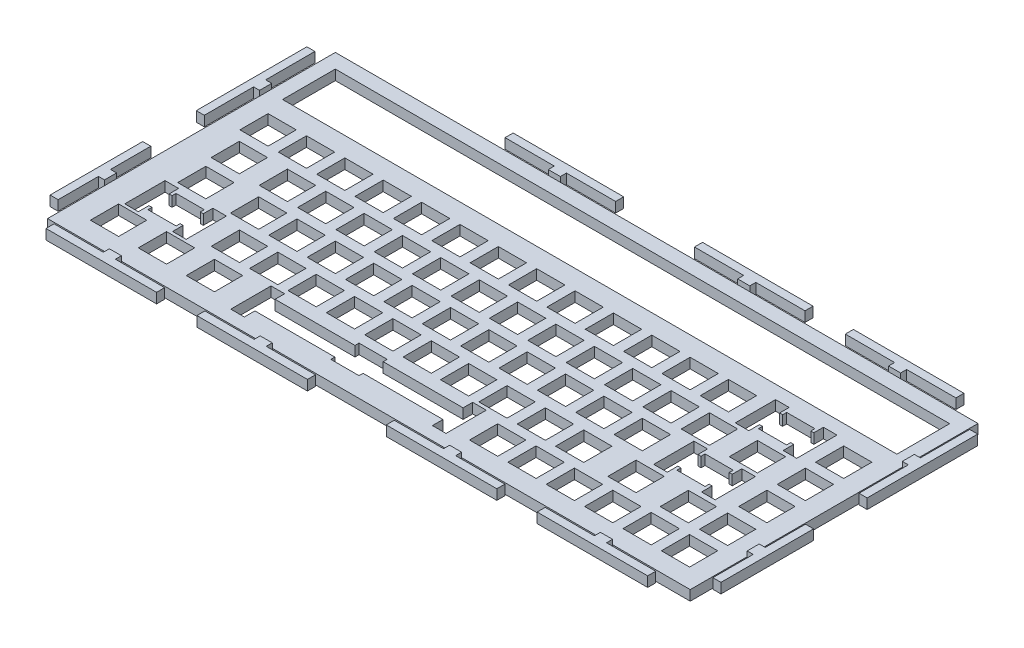
SolidWorks part; units mm, degrees
ref_plane "Front Plane" through (0, 0, 0) normal (0, 0, 1) x (1, 0, 0)
ref_plane "Top Plane" through (0, 0, 0) normal (0, 1, 0) x (1, 0, 0)
ref_plane "Right Plane" through (0, 0, 0) normal (1, 0, 0) x (0, 0, -1)
sketch "Sketch1" plane through (0, 0, 0) normal (0, 1, 0) x (1, 0, 0)
  line L2 (-75.7545, 37.9956) -> (-61.7545, 37.9956)
  line L3 (-94.8265, 37.9956) -> (-80.8265, 37.9956)
  line L4 (-94.8265, 37.9956) -> (-94.8265, 51.9956)
  line L5 (-94.8265, 51.9956) -> (-80.8265, 51.9956)
  line L6 (-80.8265, 37.9956) -> (-80.8265, 51.9956)
  line L7 (-75.7545, 37.9956) -> (-75.7545, 51.9956)
  line L8 (-75.7545, 51.9956) -> (-61.7545, 51.9956)
  line L9 (-61.7545, 37.9956) -> (-61.7545, 51.9956)
  line L10 (133.7495, 37.9956) -> (147.7495, 37.9956)
  line L11 (-37.6545, 37.9956) -> (-23.6545, 37.9956)
  line L12 (-56.7045, 37.9956) -> (-42.7045, 37.9956)
  line L13 (-56.7045, 37.9956) -> (-56.7045, 51.9956)
  line L14 (-56.7045, 51.9956) -> (-42.7045, 51.9956)
  line L15 (-42.7045, 37.9956) -> (-42.7045, 51.9956)
  line L16 (-37.6545, 37.9956) -> (-37.6545, 51.9956)
  line L17 (-37.6545, 51.9956) -> (-23.6545, 51.9956)
  line L18 (-23.6545, 37.9956) -> (-23.6545, 51.9956)
  line L19 (133.7495, 37.9956) -> (133.7495, 51.9956)
  line L20 (133.7495, 51.9956) -> (147.7495, 51.9956)
  line L21 (0.4455, 37.9956) -> (14.4455, 37.9956)
  line L22 (-18.6045, 37.9956) -> (-4.6045, 37.9956)
  line L23 (-18.6045, 37.9956) -> (-18.6045, 51.9956)
  line L24 (-18.6045, 51.9956) -> (-4.6045, 51.9956)
  line L25 (-4.6045, 37.9956) -> (-4.6045, 51.9956)
  line L26 (0.4455, 37.9956) -> (0.4455, 51.9956)
  line L27 (0.4455, 51.9956) -> (14.4455, 51.9956)
  line L28 (14.4455, 37.9956) -> (14.4455, 51.9956)
  line L29 (147.7495, 37.9956) -> (147.7495, 51.9956)
  line L30 (38.5455, 37.9956) -> (52.5455, 37.9956)
  line L31 (19.4955, 37.9956) -> (33.4955, 37.9956)
  line L32 (19.4955, 37.9956) -> (19.4955, 51.9956)
  line L33 (19.4955, 51.9956) -> (33.4955, 51.9956)
  line L34 (33.4955, 37.9956) -> (33.4955, 51.9956)
  line L35 (38.5455, 37.9956) -> (38.5455, 51.9956)
  line L36 (38.5455, 51.9956) -> (52.5455, 51.9956)
  line L37 (52.5455, 37.9956) -> (52.5455, 51.9956)
  line L38 (147.7495, 44.9956) -> (154.1495, 44.9956) construction
  line L39 (167.1835, 18.9456) -> (181.1835, 18.9456)
  line L40 (167.1835, 18.9456) -> (167.1835, 32.9456)
  line L41 (76.6455, 37.9956) -> (90.6455, 37.9956)
  line L42 (57.5955, 37.9956) -> (71.5955, 37.9956)
  line L43 (57.5955, 37.9956) -> (57.5955, 51.9956)
  line L44 (57.5955, 51.9956) -> (71.5955, 51.9956)
  line L45 (71.5955, 37.9956) -> (71.5955, 51.9956)
  line L46 (76.6455, 37.9956) -> (76.6455, 51.9956)
  line L47 (76.6455, 51.9956) -> (90.6455, 51.9956)
  line L48 (90.6455, 37.9956) -> (90.6455, 51.9956)
  line L49 (167.1835, 32.9456) -> (181.1835, 32.9456)
  line L50 (114.7225, 37.9956) -> (128.7225, 37.9956)
  line L51 (95.6955, 37.9956) -> (109.6955, 37.9956)
  line L52 (95.6955, 37.9956) -> (95.6955, 51.9956)
  line L53 (95.6955, 51.9956) -> (109.6955, 51.9956)
  line L54 (109.6955, 37.9956) -> (109.6955, 51.9956)
  line L55 (114.7225, 37.9956) -> (114.7225, 51.9956)
  line L56 (114.7225, 51.9956) -> (128.7225, 51.9956)
  line L57 (128.7225, 37.9956) -> (128.7225, 51.9956)
  line L58 (181.1835, 18.9456) -> (181.1835, 32.9456)
  line L59 (157.3735, 25.9456) -> (167.1835, 25.9456) construction
  line L73 (162.3995, 52.2456) -> (176.3995, 52.2456)
  line L75 (176.3995, 38.2456) -> (162.3995, 38.2456)
  line L77 (176.3995, 52.2456) -> (176.3995, 50.2456)
  line L78 (176.3995, 50.2456) -> (177.8995, 50.2456)
  line L79 (177.8995, 50.2456) -> (177.8995, 54.9956)
  line L80 (177.8995, 54.9956) -> (184.6495, 54.9956)
  line L81 (184.6495, 54.9956) -> (184.6495, 34.9956)
  line L82 (184.6495, 34.9956) -> (177.8995, 34.9956)
  line L83 (177.8995, 34.9956) -> (177.8995, 40.2456)
  line L84 (177.8995, 40.2456) -> (176.3995, 40.2456)
  line L85 (176.3995, 40.2456) -> (176.3995, 38.2456)
  line L86 (162.3995, 52.2456) -> (162.3995, 50.2456)
  line L87 (160.8995, 54.9956) -> (160.8995, 50.2456)
  line L88 (160.8995, 50.2456) -> (162.3995, 50.2456)
  line L89 (160.8995, 54.9956) -> (154.1495, 54.9956)
  line L90 (154.1495, 54.9956) -> (154.1495, 34.9956)
  line L91 (154.1495, 34.9956) -> (160.8995, 34.9956)
  line L92 (160.8995, 34.9956) -> (160.8995, 40.2456)
  line L93 (160.8995, 40.2456) -> (162.3995, 40.2456)
  line L94 (162.3995, 40.2456) -> (162.3995, 38.2456)
  line L116 (-47.1265, 18.9456) -> (-33.1265, 18.9456)
  line L117 (-66.1765, 18.9456) -> (-52.1765, 18.9456)
  line L118 (-66.1765, 18.9456) -> (-66.1765, 32.9456)
  line L119 (-66.1765, 32.9456) -> (-52.1765, 32.9456)
  line L120 (-52.1765, 18.9456) -> (-52.1765, 32.9456)
  line L121 (-47.1265, 18.9456) -> (-47.1265, 32.9456)
  line L122 (-47.1265, 32.9456) -> (-33.1265, 32.9456)
  line L123 (-33.1265, 18.9456) -> (-33.1265, 32.9456)
  line L125 (-9.0515, 18.9456) -> (4.9485, 18.9456)
  line L126 (-28.0765, 18.9456) -> (-14.0765, 18.9456)
  line L127 (-28.0765, 18.9456) -> (-28.0765, 32.9456)
  line L128 (-28.0765, 32.9456) -> (-14.0765, 32.9456)
  line L129 (-14.0765, 18.9456) -> (-14.0765, 32.9456)
  line L130 (-9.0515, 18.9456) -> (-9.0515, 32.9456)
  line L131 (-9.0515, 32.9456) -> (4.9485, 32.9456)
  line L132 (4.9485, 18.9456) -> (4.9485, 32.9456)
  line L135 (29.0735, 18.9456) -> (43.0735, 18.9456)
  line L136 (9.9485, 18.9456) -> (23.9485, 18.9456)
  line L137 (9.9485, 18.9456) -> (9.9485, 32.9456)
  line L138 (9.9485, 32.9456) -> (23.9485, 32.9456)
  line L139 (23.9485, 18.9456) -> (23.9485, 32.9456)
  line L140 (29.0735, 18.9456) -> (29.0735, 32.9456)
  line L141 (29.0735, 32.9456) -> (43.0735, 32.9456)
  line L142 (43.0735, 18.9456) -> (43.0735, 32.9456)
  line L144 (67.1485, 18.9456) -> (81.1485, 18.9456)
  line L145 (48.1235, 18.9456) -> (62.1235, 18.9456)
  line L146 (48.1235, 18.9456) -> (48.1235, 32.9456)
  line L147 (48.1235, 32.9456) -> (62.1235, 32.9456)
  line L148 (62.1235, 18.9456) -> (62.1235, 32.9456)
  line L149 (67.1485, 18.9456) -> (67.1485, 32.9456)
  line L150 (67.1485, 32.9456) -> (81.1485, 32.9456)
  line L151 (81.1485, 18.9456) -> (81.1485, 32.9456)
  line L152 (159.9865, 14.1456) -> (173.9865, 14.1456)
  line L153 (-42.3635, -0.1044) -> (-28.3635, -0.1044)
  line L154 (-61.4135, -0.1044) -> (-47.4135, -0.1044)
  line L155 (105.2735, 18.9456) -> (119.2735, 18.9456)
  line L156 (86.2235, 18.9456) -> (100.2235, 18.9456)
  line L157 (86.2235, 18.9456) -> (86.2235, 32.9456)
  line L158 (86.2235, 32.9456) -> (100.2235, 32.9456)
  line L159 (100.2235, 18.9456) -> (100.2235, 32.9456)
  line L160 (105.2735, 18.9456) -> (105.2735, 32.9456)
  line L161 (105.2735, 32.9456) -> (119.2735, 32.9456)
  line L162 (119.2735, 18.9456) -> (119.2735, 32.9456)
  line L163 (-61.4135, -0.1044) -> (-61.4135, 13.8956)
  line L172 (-94.8265, 37.9956) -> (-94.8265, 32.9456) construction
  line L173 (-61.4135, 13.8956) -> (-47.4135, 13.8956)
  line L174 (-47.4135, -0.1044) -> (-47.4135, 13.8956)
  line L175 (-90.0635, 18.9456) -> (-76.0635, 18.9456)
  line L176 (-90.0635, 18.9456) -> (-90.0635, 32.9456)
  line L177 (-90.0635, 32.9456) -> (-76.0635, 32.9456)
  line L178 (-76.0635, 18.9456) -> (-76.0635, 32.9456)
  line L179 (-94.8265, 32.9456) -> (-90.0635, 32.9456) construction
  line L180 (124.3235, 18.9456) -> (138.3235, 18.9456)
  line L185 (124.3235, 18.9456) -> (124.3235, 32.9456)
  line L186 (124.3235, 32.9456) -> (138.3235, 32.9456)
  line L187 (138.3235, 18.9456) -> (138.3235, 32.9456)
  line L188 (-42.3635, -0.1044) -> (-42.3635, 13.8956)
  line L189 (143.3735, 18.9456) -> (157.3735, 18.9456)
  line L190 (143.3735, 18.9456) -> (143.3735, 32.9456)
  line L191 (143.3735, 32.9456) -> (157.3735, 32.9456)
  line L192 (157.3735, 18.9456) -> (157.3735, 32.9456)
  line L193 (-42.3635, 13.8956) -> (-28.3635, 13.8956)
  line L194 (-28.3635, -0.1044) -> (-28.3635, 13.8956)
  line L195 (-4.2635, -0.1044) -> (9.7365, -0.1044)
  line L196 (-23.3135, -0.1044) -> (-9.3135, -0.1044)
  line L197 (-23.3135, -0.1044) -> (-23.3135, 13.8956)
  line L198 (-23.3135, 13.8956) -> (-9.3135, 13.8956)
  line L199 (-9.3135, -0.1044) -> (-9.3135, 13.8956)
  line L200 (-4.2635, -0.1044) -> (-4.2635, 13.8956)
  line L201 (-4.2635, 13.8956) -> (9.7365, 13.8956)
  line L202 (9.7365, -0.1044) -> (9.7365, 13.8956)
  line L203 (33.8365, -0.1044) -> (47.8365, -0.1044)
  line L204 (14.7865, -0.1044) -> (28.7865, -0.1044)
  line L205 (14.7865, -0.1044) -> (14.7865, 13.8956)
  line L206 (14.7865, 13.8956) -> (28.7865, 13.8956)
  line L207 (28.7865, -0.1044) -> (28.7865, 13.8956)
  line L208 (33.8365, -0.1044) -> (33.8365, 13.8956)
  line L209 (33.8365, 13.8956) -> (47.8365, 13.8956)
  line L210 (47.8365, -0.1044) -> (47.8365, 13.8956)
  line L211 (71.9365, -0.1044) -> (85.9365, -0.1044)
  line L212 (52.8865, -0.1044) -> (66.8865, -0.1044)
  line L213 (52.8865, -0.1044) -> (52.8865, 13.8956)
  line L214 (52.8865, 13.8956) -> (66.8865, 13.8956)
  line L215 (66.8865, -0.1044) -> (66.8865, 13.8956)
  line L216 (71.9365, -0.1044) -> (71.9365, 13.8956)
  line L217 (71.9365, 13.8956) -> (85.9365, 13.8956)
  line L218 (85.9365, -0.1044) -> (85.9365, 13.8956)
  line L219 (110.0365, -0.1044) -> (124.0365, -0.1044)
  line L220 (90.9865, -0.1044) -> (104.9865, -0.1044)
  line L221 (90.9865, -0.1044) -> (90.9865, 13.8956)
  line L222 (90.9865, 13.8956) -> (104.9865, 13.8956)
  line L223 (104.9865, -0.1044) -> (104.9865, 13.8956)
  line L224 (110.0365, -0.1044) -> (110.0365, 13.8956)
  line L225 (110.0365, 13.8956) -> (124.0365, 13.8956)
  line L226 (124.0365, -0.1044) -> (124.0365, 13.8956)
  line L227 (-87.6075, -0.1044) -> (-73.6075, -0.1044)
  line L228 (-87.6075, -0.1044) -> (-87.6075, 13.8956)
  line L229 (-87.6075, 13.8956) -> (-73.6075, 13.8956)
  line L230 (-73.6075, -0.1044) -> (-73.6075, 13.8956)
  line L231 (-90.0635, 18.9456) -> (-90.0635, 13.8956) construction
  line L232 (129.0865, -0.1044) -> (143.0865, -0.1044)
  line L233 (129.0865, -0.1044) -> (129.0865, 13.8956)
  line L234 (129.0865, 13.8956) -> (143.0865, 13.8956)
  line L235 (143.0865, -0.1044) -> (143.0865, 13.8956)
  line L240 (-90.0635, 13.8956) -> (-87.6075, 13.8956) construction
  line L241 (173.9865, 0.1456) -> (159.9865, 0.1456)
  line L242 (173.9865, 14.1456) -> (173.9865, 12.1456)
  line L243 (173.9865, 12.1456) -> (175.4865, 12.1456)
  line L244 (175.4865, 12.1456) -> (175.4865, 16.8956)
  line L245 (175.4865, 16.8956) -> (182.2365, 16.8956)
  line L246 (182.2365, 16.8956) -> (182.2365, -3.1044)
  line L247 (182.2365, -3.1044) -> (175.4865, -3.1044)
  line L248 (175.4865, -3.1044) -> (175.4865, 2.1456)
  line L249 (175.4865, 2.1456) -> (173.9865, 2.1456)
  line L250 (173.9865, 2.1456) -> (173.9865, 0.1456)
  line L251 (159.9865, 14.1456) -> (159.9865, 12.1456)
  line L252 (158.4865, 16.8956) -> (158.4865, 12.1456)
  line L253 (158.4865, 12.1456) -> (159.9865, 12.1456)
  line L254 (158.4865, 16.8956) -> (151.7365, 16.8956)
  line L255 (151.7365, 16.8956) -> (151.7365, -3.1044)
  line L256 (151.7365, -3.1044) -> (158.4865, -3.1044)
  line L257 (158.4865, -3.1044) -> (158.4865, 2.1456)
  line L258 (158.4865, 2.1456) -> (159.9865, 2.1456)
  line L259 (159.9865, 2.1456) -> (159.9865, 0.1456)
  line L260 (143.0865, 12.1456) -> (151.7365, 12.1456) construction
  line L262 (-32.8385, -19.1544) -> (-18.8385, -19.1544)
  line L263 (-51.8885, -19.1544) -> (-37.8885, -19.1544)
  line L264 (-51.8885, -19.1544) -> (-51.8885, -5.1544)
  line L265 (-51.8885, -5.1544) -> (-37.8885, -5.1544)
  line L266 (-37.8885, -19.1544) -> (-37.8885, -5.1544)
  line L267 (-32.8385, -19.1544) -> (-32.8385, -5.1544)
  line L268 (-32.8385, -5.1544) -> (-18.8385, -5.1544)
  line L269 (-18.8385, -19.1544) -> (-18.8385, -5.1544)
  line L270 (5.2615, -19.1544) -> (19.2615, -19.1544)
  line L271 (-13.7885, -19.1544) -> (0.2115, -19.1544)
  line L272 (-13.7885, -19.1544) -> (-13.7885, -5.1544)
  line L273 (-13.7885, -5.1544) -> (0.2115, -5.1544)
  line L274 (0.2115, -19.1544) -> (0.2115, -5.1544)
  line L275 (5.2615, -19.1544) -> (5.2615, -5.1544)
  line L276 (5.2615, -5.1544) -> (19.2615, -5.1544)
  line L277 (19.2615, -19.1544) -> (19.2615, -5.1544)
  line L278 (43.3615, -19.1544) -> (57.3615, -19.1544)
  line L279 (24.3115, -19.1544) -> (38.3115, -19.1544)
  line L280 (24.3115, -19.1544) -> (24.3115, -5.1544)
  line L281 (24.3115, -5.1544) -> (38.3115, -5.1544)
  line L282 (38.3115, -19.1544) -> (38.3115, -5.1544)
  line L283 (43.3615, -19.1544) -> (43.3615, -5.1544)
  line L284 (43.3615, -5.1544) -> (57.3615, -5.1544)
  line L285 (57.3615, -19.1544) -> (57.3615, -5.1544)
  line L286 (81.4615, -19.6544) -> (95.4615, -19.6544)
  line L287 (62.4115, -19.6544) -> (76.4115, -19.6544)
  line L288 (62.4115, -19.6544) -> (62.4115, -5.6544)
  line L289 (62.4115, -5.6544) -> (76.4115, -5.6544)
  line L290 (76.4115, -19.6544) -> (76.4115, -5.6544)
  line L291 (81.4615, -19.6544) -> (81.4615, -5.6544)
  line L292 (81.4615, -5.6544) -> (95.4615, -5.6544)
  line L293 (95.4615, -19.6544) -> (95.4615, -5.6544)
  line L294 (119.5615, -19.6544) -> (133.5615, -19.6544)
  line L295 (100.5115, -19.6544) -> (114.5115, -19.6544)
  line L296 (100.5115, -19.6544) -> (100.5115, -5.6544)
  line L297 (100.5115, -5.6544) -> (114.5115, -5.6544)
  line L298 (114.5115, -19.6544) -> (114.5115, -5.6544)
  line L299 (119.5615, -19.6544) -> (119.5615, -5.6544)
  line L300 (119.5615, -5.6544) -> (133.5615, -5.6544)
  line L301 (133.5615, -19.6544) -> (133.5615, -5.6544)
  line L306 (-83.3445, -5.1544) -> (-69.3445, -5.1544)
  line L307 (145.5235, -19.6544) -> (159.5235, -19.6544)
  line L308 (145.5235, -19.6544) -> (145.5235, -5.6544)
  line L309 (145.5235, -5.6544) -> (159.5235, -5.6544)
  line L310 (159.5235, -19.6544) -> (159.5235, -5.6544)
  line L311 (-69.3445, -19.1544) -> (-83.3445, -19.1544)
  line L331 (171.4855, -19.6544) -> (185.4855, -19.6544)
  line L332 (171.4855, -19.6544) -> (171.4855, -5.6544)
  line L333 (171.4855, -5.6544) -> (185.4855, -5.6544)
  line L334 (185.4855, -19.6544) -> (185.4855, -5.6544)
  line L335 (159.5235, -12.6544) -> (171.4855, -12.6544) construction
  line L336 (-61.4135, -0.1044) -> (-61.4135, -5.1544) construction
  line L337 (-61.4135, -5.1544) -> (-51.8885, -5.1544) construction
  line L338 (-104.4215, 94.9896) -> (-117.5239, 94.9896) construction
  line L339 (-97.2765, 61.6456) -> (207.7235, 61.6456)
  line L340 (190.9955, 18.9456) -> (204.9955, 18.9456)
  line L341 (190.9955, 18.9456) -> (190.9955, 32.9456)
  line L342 (190.9955, 32.9456) -> (204.9955, 32.9456)
  line L343 (204.9955, 18.9456) -> (204.9955, 32.9456)
  line L344 (181.1835, 25.9456) -> (190.9955, 25.9456) construction
  line L345 (190.9745, 37.9956) -> (204.9745, 37.9956)
  line L346 (190.9745, 37.9956) -> (190.9745, 51.9956)
  line L347 (190.9745, 51.9956) -> (204.9745, 51.9956)
  line L348 (204.9745, 37.9956) -> (204.9745, 51.9956)
  line L349 (184.6495, 44.9956) -> (190.9745, 44.9956) construction
  line L350 (190.9425, -0.1044) -> (204.9425, -0.1044)
  line L351 (190.9425, -0.1044) -> (190.9425, 13.8956)
  line L352 (190.9425, 13.8956) -> (204.9425, 13.8956)
  line L353 (204.9425, -0.1044) -> (204.9425, 13.8956)
  line L354 (182.2365, 6.8956) -> (190.9425, 6.8956) construction
  line L355 (190.9855, -19.6544) -> (204.9855, -19.6544)
  line L356 (190.9855, -19.6544) -> (190.9855, -5.6544)
  line L357 (190.9855, -5.6544) -> (204.9855, -5.6544)
  line L358 (204.9855, -19.6544) -> (204.9855, -5.6544)
  line L359 (185.4855, -12.6544) -> (190.9855, -12.6544) construction
  line L360 (-69.3445, -5.1544) -> (-69.3445, -7.1544)
  line L361 (-69.3445, -7.1544) -> (-67.8445, -7.1544)
  line L362 (-67.8445, -7.1544) -> (-67.8445, -2.4044)
  line L363 (-67.8445, -2.4044) -> (-61.0945, -2.4044)
  line L364 (-61.0945, -2.4044) -> (-61.0945, -22.4044)
  line L365 (-61.0945, -22.4044) -> (-67.8445, -22.4044)
  line L366 (-67.8445, -22.4044) -> (-67.8445, -17.1544)
  line L367 (-67.8445, -17.1544) -> (-69.3445, -17.1544)
  line L368 (-69.3445, -17.1544) -> (-69.3445, -19.1544)
  line L369 (-83.3445, -5.1544) -> (-83.3445, -7.1544)
  line L370 (-84.8445, -2.4044) -> (-84.8445, -7.1544)
  line L371 (-84.8445, -7.1544) -> (-83.3445, -7.1544)
  line L372 (-84.8445, -2.4044) -> (-91.5945, -2.4044)
  line L373 (-91.5945, -2.4044) -> (-91.5945, -22.4044)
  line L374 (-91.5945, -22.4044) -> (-84.8445, -22.4044)
  line L375 (-84.8445, -22.4044) -> (-84.8445, -17.1544)
  line L376 (-84.8445, -17.1544) -> (-83.3445, -17.1544)
  line L377 (-83.3445, -17.1544) -> (-83.3445, -19.1544)
  line L378 (-93.0945, -37.9544) -> (-79.0945, -37.9544)
  line L379 (-93.0945, -37.9544) -> (-93.0945, -23.9544)
  line L380 (-93.0945, -23.9544) -> (-79.0945, -23.9544)
  line L381 (-79.0945, -37.9544) -> (-79.0945, -23.9544)
  line L382 (-69.2945, -37.9544) -> (-55.2945, -37.9544)
  line L383 (-69.2945, -37.9544) -> (-69.2945, -23.9544)
  line L384 (-69.2945, -23.9544) -> (-55.2945, -23.9544)
  line L385 (-55.2945, -37.9544) -> (-55.2945, -23.9544)
  line L390 (-45.4945, -37.9544) -> (-31.4945, -37.9544)
  line L391 (-45.4945, -37.9544) -> (-45.4945, -23.9544)
  line L392 (-45.4945, -23.9544) -> (-31.4945, -23.9544)
  line L393 (-31.4945, -37.9544) -> (-31.4945, -23.9544)
  line L394 (-55.2945, -23.9544) -> (-45.4945, -23.9544) construction
  line L395 (26.4395, -24.1144) -> (40.4395, -24.1144)
  line L396 (40.4395, -38.1144) -> (26.4395, -38.1144)
  line L397 (40.4395, -24.1144) -> (40.4395, -26.1144)
  line L398 (40.4395, -26.1144) -> (80.1235, -26.1144)
  line L399 (80.1235, -26.1144) -> (80.1235, -21.3644)
  line L400 (80.1235, -21.3644) -> (86.8735, -21.3644)
  line L401 (86.8735, -21.3644) -> (86.8735, -41.3644)
  line L402 (86.8735, -41.3644) -> (80.1235, -41.3644)
  line L403 (80.1235, -41.3644) -> (80.1235, -36.1144)
  line L404 (80.1235, -36.1144) -> (40.4395, -36.1144)
  line L405 (40.4395, -36.1144) -> (40.4395, -38.1144)
  line L406 (26.4395, -24.1144) -> (26.4395, -26.1144)
  line L407 (-13.2445, -21.3644) -> (-13.2445, -26.1144)
  line L408 (-13.2445, -26.1144) -> (26.4395, -26.1144)
  line L409 (-13.2445, -21.3644) -> (-19.9945, -21.3644)
  line L410 (-19.9945, -21.3644) -> (-19.9945, -41.3644)
  line L411 (-19.9945, -41.3644) -> (-13.2445, -41.3644)
  line L412 (-13.2445, -41.3644) -> (-13.2445, -36.1144)
  line L413 (-13.2445, -36.1144) -> (26.4395, -36.1144)
  line L414 (26.4395, -36.1144) -> (26.4395, -38.1144)
  line L415 (95.5435, -38.3644) -> (109.5435, -38.3644)
  line L416 (95.5435, -38.3644) -> (95.5435, -24.3644)
  line L417 (95.5435, -24.3644) -> (109.5435, -24.3644)
  line L418 (109.5435, -38.3644) -> (109.5435, -24.3644)
  line L419 (86.8735, -31.3644) -> (95.5435, -31.3644) construction
  line L420 (114.5935, -38.3644) -> (128.5935, -38.3644)
  line L421 (114.5935, -38.3644) -> (114.5935, -24.3644)
  line L422 (114.5935, -24.3644) -> (128.5935, -24.3644)
  line L423 (128.5935, -38.3644) -> (128.5935, -24.3644)
  line L424 (114.5935, -31.3644) -> (109.5435, -31.3644) construction
  line L425 (133.6435, -38.3644) -> (147.6435, -38.3644)
  line L426 (133.6435, -38.3644) -> (133.6435, -24.3644)
  line L427 (133.6435, -24.3644) -> (147.6435, -24.3644)
  line L428 (147.6435, -38.3644) -> (147.6435, -24.3644)
  line L429 (152.6935, -38.3644) -> (166.6935, -38.3644)
  line L430 (152.6935, -38.3644) -> (152.6935, -24.3644)
  line L431 (152.6935, -24.3644) -> (166.6935, -24.3644)
  line L432 (166.6935, -38.3644) -> (166.6935, -24.3644)
  line L433 (171.7435, -38.3644) -> (185.7435, -38.3644)
  line L434 (171.7435, -38.3644) -> (171.7435, -24.3644)
  line L435 (171.7435, -24.3644) -> (185.7435, -24.3644)
  line L436 (185.7435, -38.3644) -> (185.7435, -24.3644)
  line L437 (190.7935, -38.3644) -> (204.7935, -38.3644)
  line L438 (190.7935, -38.3644) -> (190.7935, -24.3644)
  line L439 (190.7935, -24.3644) -> (204.7935, -24.3644)
  line L440 (204.7935, -38.3644) -> (204.7935, -24.3644)
  line L441 (-97.2765, 61.6456) -> (-97.2765, 87.8456)
  line L442 (-97.2765, 87.8456) -> (207.7235, 87.8456)
  line L443 (207.7235, 61.6456) -> (207.7235, 87.8456)
  line L444 (-104.4215, 94.9896) -> (214.6585, 94.9896)
  line L445 (-104.4215, 94.9896) -> (-104.4215, -47.8854)
  line L446 (-104.4215, -47.8854) -> (214.6585, -47.8854)
  line L447 (214.6585, 94.9896) -> (214.6585, -47.8854)
  line L448 (-117.5239, 94.9896) -> (-117.5239, 25.8096) construction
  line L449 (-104.4215, -47.8854) -> (-117.5239, -47.8854) construction
  line L450 (-117.5239, -47.8854) -> (-117.5239, 14.6046) construction
  line L451 (-150.5498, 25.8096) -> (-98.6233, 25.8096) construction
  line L452 (-150.5498, 14.6046) -> (-97.2765, 14.6046) construction
  line L453 (-104.4215, 94.9896) -> (-104.4215, 60.3996) construction
  point P115 (128.7225, 44.9956)
  point P116 (154.1495, 44.9956)
  dimension "D1" = 14
  dimension "D2" = 20
  dimension "D3" = 4.75
  dimension "D4" = 6.75
  dimension "D5" = 1.5
  dimension "D6" = 2
  dimension "D13" = 14
  dimension "D14" = 14
  dimension "D15" = 5.072
  dimension "D16" = 14
  dimension "D17" = 5.05
  dimension "D18" = 5.05
  dimension "D19" = 14
  dimension "D20" = 4.763
  dimension "D21" = 5.05
  dimension "D22" = 9.887
  dimension "D23" = 26.2
  dimension "D24" = 14
  dimension "D25" = 14
  dimension "D26" = 5.05
  dimension "D27" = 5.05
  dimension "D28" = 5.05
  dimension "D29" = 5.05
  dimension "D30" = 5.05
  dimension "D31" = 5.05
  dimension "D32" = 5.05
  dimension "D33" = 5.05
  dimension "D34" = 5.05
  dimension "D35" = 5.027
  dimension "D36" = 5.05
  dimension "D37" = 5.05
  dimension "D38" = 5.025
  dimension "D39" = 5
  dimension "D40" = 5.125
  dimension "D41" = 5.05
  dimension "D42" = 5.025
  dimension "D43" = 5.075
  dimension "D44" = 5.05
  dimension "D45" = 5.05
  dimension "D46" = 5.027
  dimension "D47" = 14.65
  dimension "D48" = 14
  dimension "D49" = 9.81
  dimension "D50" = 12.194
  dimension "D51" = 5.05
  dimension "D52" = 5.05
  dimension "D53" = 5.05
  dimension "D54" = 5.05
  dimension "D55" = 5.05
  dimension "D56" = 5.05
  dimension "D57" = 5.05
  dimension "D58" = 5.05
  dimension "D59" = 5.05
  dimension "D60" = 5.05
  dimension "D61" = 14
  dimension "D62" = 20
  dimension "D63" = 5.05
  dimension "D64" = 2.456
  dimension "D65" = 4.75
  dimension "D66" = 6.75
  dimension "D67" = 1.5
  dimension "D68" = 2
  dimension "D69" = 16.9
  dimension "D70" = 14
  dimension "D71" = 5.05
  dimension "D72" = 5.05
  dimension "D73" = 5.05
  dimension "D74" = 5.05
  dimension "D75" = 5.05
  dimension "D76" = 5.05
  dimension "D77" = 5.05
  dimension "D78" = 5.05
  dimension "D79" = 5.05
  dimension "D80" = 11.962
  dimension "D81" = 20
  dimension "D82" = 14
  dimension "D83" = 11.962
  dimension "D84" = 14
  dimension "D85" = 14
  dimension "D86" = 9.812
  dimension "D87" = 14
  dimension "D88" = 14.575
  dimension "D89" = 4.75
  dimension "D90" = 14
  dimension "D91" = 6.75
  dimension "D92" = 14
  dimension "D93" = 16.956
  dimension "D94" = 14
  dimension "D95" = 5.5
  dimension "D96" = 5.05
  dimension "D97" = 5.05
  dimension "D98" = 9.525
  dimension "D99" = 1.5
  dimension "D100" = 2
  dimension "D101" = 5.05
  dimension "D102" = 9.206
  dimension "D103" = 5.05
  dimension "D104" = 14
  dimension "D105" = 14
  dimension "D106" = 14
  dimension "D107" = 14
  dimension "D108" = 1.5
  dimension "D109" = 9.8
  dimension "D110" = 5.05
  dimension "D111" = 9.8
  dimension "D112" = 5.05
  dimension "D113" = 5.05
  dimension "D114" = 14
  dimension "D115" = 14
  dimension "D116" = 20
  dimension "D117" = 4.75
  dimension "D118" = 6.75
  dimension "D119" = 39.684
  dimension "D120" = 2
  dimension "D121" = 5.05
  dimension "D122" = 11.5
  dimension "D123" = 14
  dimension "D124" = 8.67
  dimension "D125" = 5.25
  dimension "D126" = 14
  dimension "D127" = 5.05
  dimension "D128" = 14
  dimension "D129" = 14
  dimension "D130" = 14
  dimension "D131" = 14
  dimension "D132" = 5.05
  dimension "D133" = 5.05
  dimension "D134" = 5.05
  dimension "D135" = 5.05
  dimension "D136" = 4.8
  dimension "D137" = 5.25
  dimension "D138" = 5.25
  dimension "D139" = 5.25
  dimension "D140" = 305
  dimension "D141" = 9.65
  dimension "D142" = 142.875
  dimension "D143" = 319.08
  dimension "D144" = 7.144
  dimension "D145" = 7.145
  dimension "D146" = 2.45
  dimension "D147" = 69.18
  dimension "D148" = 62.49
extrude "Boss-Extrude2" add sketch "Sketch1" along normal mid plane 5
sketch "Sketch2" plane through (0, 2.5, 0) normal (0, 1, 0) x (1, 0, 0)
  line L0 (-104.4215, 25.7896) -> (-104.4215, 14.6146) construction
  line L1 (-104.4215, -47.8854) -> (-104.4215, 14.6146) construction
  line L2 (-104.4215, 94.9896) -> (-104.4215, -47.8854) construction
  line L3 (-104.4215, 94.9896) -> (-104.4215, 25.7896) construction
  line L4 (-104.4215, 60.3896) -> (-192.4203, 60.3896) construction
  line L5 (-104.4215, 63.3896) -> (-104.4215, 57.3896)
  line L6 (-104.4215, 63.3896) -> (-107.4215, 63.3896)
  line L7 (-104.4215, 57.3896) -> (-107.4215, 57.3896)
  line L8 (-107.4215, 63.3896) -> (-107.4215, 87.8456)
  line L9 (-107.4215, 57.3896) -> (-107.4215, 32.9456)
  line L10 (-107.4215, 87.8456) -> (-111.4215, 87.8456)
  line L11 (-111.4215, 87.8456) -> (-111.4215, 32.9456)
  line L12 (-111.4215, 32.9456) -> (-107.4215, 32.9456)
  line L13 (207.7235, 87.8456) -> (-97.2765, 87.8456) construction
  line L14 (-107.4215, 20.2021) -> (-104.4215, 20.2021) construction
  line L15 (-76.0635, 32.9456) -> (-90.0635, 32.9456) construction
  line L16 (-107.4215, 31.2421) -> (-107.4215, 9.1621) construction
  line L17 (-104.4215, -13.6354) -> (-104.4215, -19.6354)
  line L18 (-104.4215, -13.6354) -> (-107.4215, -13.6354)
  line L19 (-104.4215, -19.6354) -> (-107.4215, -19.6354)
  line L20 (-107.4215, -13.6354) -> (-107.4215, 6.3646)
  line L21 (-107.4215, 6.3646) -> (-111.4215, 6.3646)
  line L22 (-111.4215, 6.3646) -> (-111.4215, -39.6354)
  line L23 (-111.4215, -39.6354) -> (-107.4215, -39.6354)
  line L24 (-107.4215, -39.6354) -> (-107.4215, -19.6354)
  line L25 (214.6585, 14.5646) -> (214.6585, -47.8854) construction
  line L26 (55.1185, 125.0144) -> (55.1185, -78.0627) construction
  line L27 (221.6585, -39.6354) -> (217.6585, -39.6354)
  line L28 (221.6585, 6.3646) -> (221.6585, -39.6354)
  line L29 (217.6585, 6.3646) -> (221.6585, 6.3646)
  line L30 (217.6585, -13.6354) -> (217.6585, 6.3646)
  line L31 (214.6585, -13.6354) -> (217.6585, -13.6354)
  line L32 (214.6585, -13.6354) -> (214.6585, -19.6354)
  line L33 (214.6585, -19.6354) -> (217.6585, -19.6354)
  line L34 (217.6585, -39.6354) -> (217.6585, -19.6354)
  line L35 (214.6585, 63.3896) -> (217.6585, 63.3896)
  line L36 (217.6585, 63.3896) -> (217.6585, 87.8456)
  line L37 (217.6585, 87.8456) -> (221.6585, 87.8456)
  line L38 (221.6585, 87.8456) -> (221.6585, 32.9456)
  line L39 (221.6585, 32.9456) -> (217.6585, 32.9456)
  line L40 (217.6585, 57.3896) -> (217.6585, 32.9456)
  line L41 (214.6585, 57.3896) -> (217.6585, 57.3896)
  line L42 (214.6585, 63.3896) -> (214.6585, 57.3896)
  line L43 (214.6585, -47.8854) -> (214.6585, 94.9896) construction
  line L44 (214.6585, 94.9896) -> (214.6585, 25.7896) construction
  line L45 (214.6585, 25.7896) -> (214.6585, 14.5646) construction
  line L46 (214.6585, 20.1771) -> (217.6585, 20.1771) construction
  line L47 (217.6585, 31.2421) -> (217.6585, 9.1621) construction
  line L48 (55.1185, 94.9896) -> (55.1185, -47.8854) construction
  line L49 (214.6585, 94.9896) -> (-104.4215, 94.9896) construction
  line L50 (-104.4215, -47.8854) -> (214.6585, -47.8854) construction
  line L51 (55.1185, 23.4758) -> (270.1989, 23.4758) construction
  line L52 (55.1185, 23.4758) -> (-168.679, 23.4758) construction
  line L53 (214.6585, 94.9896) -> (56.9085, 94.9896) construction
  line L54 (-104.4215, 94.9896) -> (45.7235, 94.9896) construction
  line L55 (45.7235, 94.9896) -> (56.9085, 94.9896) construction
  line L56 (51.316, 94.9896) -> (51.316, 98.9896) construction
  line L57 (40.276, 98.9896) -> (62.356, 98.9896) construction
  line L58 (170.2335, 94.9896) -> (176.2335, 94.9896)
  line L59 (176.2335, 94.9896) -> (176.2335, 97.9896)
  line L60 (176.2335, 97.9896) -> (200.6835, 97.9896)
  line L61 (200.6835, 97.9896) -> (200.6835, 101.9896)
  line L62 (200.6835, 101.9896) -> (145.7835, 101.9896)
  line L63 (145.7835, 101.9896) -> (145.7835, 97.9896)
  line L64 (145.7835, 97.9896) -> (170.2335, 97.9896)
  line L65 (170.2335, 97.9896) -> (170.2335, 94.9896)
  line L66 (95.3335, 94.9896) -> (101.3335, 94.9896)
  line L67 (101.3335, 94.9896) -> (101.3335, 97.9896)
  line L68 (101.3335, 97.9896) -> (125.7835, 97.9896)
  line L69 (125.7835, 97.9896) -> (125.7835, 101.9896)
  line L70 (125.7835, 101.9896) -> (70.8835, 101.9896)
  line L71 (70.8835, 101.9896) -> (70.8835, 97.9896)
  line L72 (70.8835, 97.9896) -> (95.3335, 97.9896)
  line L73 (95.3335, 97.9896) -> (95.3335, 94.9896)
  line L74 (125.7835, 99.9896) -> (145.7835, 99.9896) construction
  line L75 (135.7835, 94.9896) -> (135.7835, 104.9896) construction
  line L84 (7.2985, 97.9896) -> (7.2985, 94.9896)
  line L85 (31.7485, 97.9896) -> (7.2985, 97.9896)
  line L86 (31.7485, 101.9896) -> (31.7485, 97.9896)
  line L87 (-23.1515, 101.9896) -> (31.7485, 101.9896)
  line L88 (-23.1515, 97.9896) -> (-23.1515, 101.9896)
  line L89 (1.2985, 97.9896) -> (-23.1515, 97.9896)
  line L90 (1.2985, 94.9896) -> (1.2985, 97.9896)
  line L91 (7.2985, 94.9896) -> (1.2985, 94.9896)
  line L92 (145.7835, -51.038) -> (170.2335, -51.038)
  line L93 (145.7835, -55.038) -> (145.7835, -51.038)
  line L94 (200.6835, -55.038) -> (145.7835, -55.038)
  line L95 (200.6835, -51.038) -> (200.6835, -55.038)
  line L96 (176.2335, -51.038) -> (200.6835, -51.038)
  line L97 (176.2335, -48.038) -> (176.2335, -51.038)
  line L98 (170.2335, -48.038) -> (176.2335, -48.038)
  line L99 (170.2335, -51.038) -> (170.2335, -48.038)
  line L100 (95.3335, -51.038) -> (95.3335, -48.038)
  line L101 (70.8835, -51.038) -> (95.3335, -51.038)
  line L102 (70.8835, -55.038) -> (70.8835, -51.038)
  line L103 (125.7835, -55.038) -> (70.8835, -55.038)
  line L104 (125.7835, -51.038) -> (125.7835, -55.038)
  line L105 (101.3335, -51.038) -> (125.7835, -51.038)
  line L106 (101.3335, -48.038) -> (101.3335, -51.038)
  line L107 (95.3335, -48.038) -> (101.3335, -48.038)
  line L108 (31.7485, -51.038) -> (7.2985, -51.038)
  line L109 (31.7485, -55.038) -> (31.7485, -51.038)
  line L110 (-23.1515, -55.038) -> (31.7485, -55.038)
  line L111 (-23.1515, -51.038) -> (-23.1515, -55.038)
  line L112 (1.2985, -51.038) -> (-23.1515, -51.038)
  line L113 (1.2985, -48.038) -> (1.2985, -51.038)
  line L114 (7.2985, -48.038) -> (1.2985, -48.038)
  line L115 (7.2985, -51.038) -> (7.2985, -48.038)
  line L116 (-43.1515, -55.038) -> (-43.1515, -51.038)
  line L117 (-98.0515, -55.038) -> (-43.1515, -55.038)
  line L118 (-98.0515, -51.038) -> (-98.0515, -55.038)
  line L119 (-73.6015, -51.038) -> (-98.0515, -51.038)
  line L120 (-73.6015, -48.038) -> (-73.6015, -51.038)
  line L121 (-67.6015, -48.038) -> (-73.6015, -48.038)
  line L122 (-67.6015, -51.038) -> (-67.6015, -48.038)
  line L123 (-43.1515, -51.038) -> (-67.6015, -51.038)
  line L124 (214.6585, -47.8854) -> (56.9135, -47.8854) construction
  line L125 (-104.4215, 94.9896) -> (-104.4215, 96.9896) construction
  line L126 (-104.4215, -47.8854) -> (45.7225, -47.8854) construction
  line L127 (45.7225, -47.8854) -> (56.9135, -47.8854) construction
  line L128 (51.318, -47.8854) -> (51.318, -52.8854) construction
  line L129 (40.276, -52.8854) -> (62.356, -52.8854) construction
  line L130 (-104.4215, 96.9896) -> (-90.2825, 96.9896) construction
  line L131 (-90.2825, 96.9896) -> (-81.3425, 96.9896) construction
  point P17 (-104.4215, 60.3896)
  point P21 (-104.4215, 60.3896)
  point P28 (-104.4215, 20.2021)
  point P31 (-104.4215, -16.6354)
  point P34 (-104.4215, -16.6354)
  point P84 (51.316, 98.9896)
  point P103 (145.7835, 99.9896)
  point P106 (135.7835, 99.9896)
  point P107 (135.7835, 99.9896)
  dimension "D1" = 69.2
  dimension "D2" = 62.5
  dimension "D3" = 3
  dimension "D4" = 6
  dimension "D5" = 0
  dimension "D6" = 0
  dimension "D7" = 22.08
  dimension "D8" = 3
  dimension "D9" = 6
  dimension "D10" = 3
  dimension "D11" = 20
  dimension "D12" = 4
  dimension "D13" = 4
  dimension "D14" = 62.45
  dimension "D15" = 69.2
  dimension "D16" = 22.08
  dimension "D17" = 157.75
  dimension "D18" = 150.145
  dimension "D19" = 4
  dimension "D20" = 22.08
  dimension "D21" = 6
  dimension "D22" = 3
  dimension "D23" = 4
  dimension "D24" = 54.9
  dimension "D25" = 6
  dimension "D26" = 3
  dimension "D27" = 4
  dimension "D28" = 54.9
  dimension "D29" = 20
  dimension "D30" = 10
  dimension "D31" = 157.745
  dimension "D32" = 150.144
  dimension "D33" = 5
  dimension "D34" = 22.08
  dimension "D35" = 2
  dimension "D36" = 14.139
  dimension "D37" = 8.94
  dimension "D38" = 159.54
  dimension "D39" = 57.0475
extrude "Boss-Extrude3" add sketch "Sketch2" along normal mid plane 5
